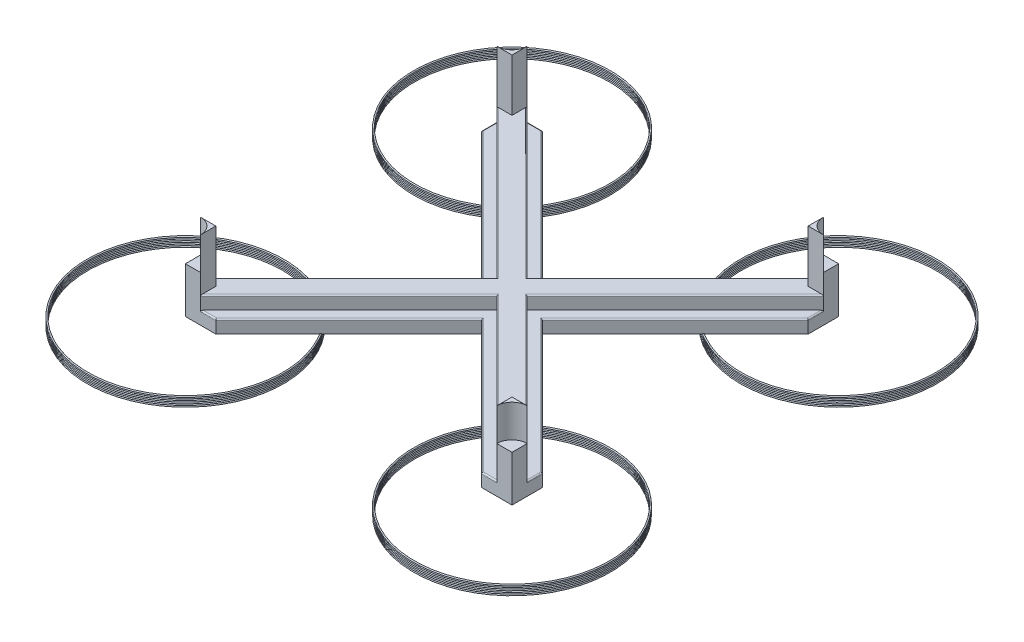
SolidWorks part; units mm, degrees
material "ABS"
ref_plane "Front Plane" through (0, 0, 0) normal (0, 0, 1) x (1, 0, 0)
ref_plane "Top Plane" through (0, 0, 0) normal (0, 1, 0) x (1, 0, 0)
ref_plane "Right Plane" through (0, 0, 0) normal (1, 0, 0) x (0, 0, -1)
sketch "Sketch1" plane through (0, 0, 0) normal (0, 1, 0) x (1, 0, 0)
  line L0 (-11.8367, 0) -> (-63.5, 51.6633)
  line L1 (-63.5, -63.5) -> (-51.6633, -63.5)
  line L2 (-63.5, -63.5) -> (-63.5, -51.6633)
  line L3 (-63.5, 63.5) -> (-51.6633, 63.5)
  line L4 (63.5, -63.5) -> (63.5, -51.6633)
  line L5 (-63.5, -63.5) -> (63.5, 63.5) construction
  line L6 (-63.5, 63.5) -> (63.5, -63.5) construction
  line L7 (0, -11.8367) -> (51.6633, -63.5)
  line L8 (0, 11.8367) -> (-51.6633, 63.5)
  line L9 (11.8367, 0) -> (63.5, -51.6633)
  line L12 (-63.5, -51.6633) -> (-11.8367, 0)
  line L13 (63.5, 51.6633) -> (11.8367, 0)
  line L16 (51.6633, 63.5) -> (63.5, 63.5)
  line L17 (63.5, 51.6633) -> (63.5, 63.5)
  line L18 (-63.5, 51.6633) -> (-63.5, 63.5)
  line L19 (51.6633, -63.5) -> (63.5, -63.5)
  line L20 (0, 11.8367) -> (51.6633, 63.5)
  line L21 (0, -11.8367) -> (-51.6633, -63.5)
  point P0 (0, 0)
extrude "Boss-Extrude1" add sketch "Sketch1" along normal blind 5.08
ref_plane "Plane3" through (0, 0, 0) normal (0, 0, -1) x (-1, 0, 0)
ref_plane "Plane1" through (0, 0, 0) normal (0.7071, 0, -0.7071) x (-0.7071, 0, -0.7071)
ref_plane "Plane2" through (0, 0, 0) normal (1, 0, 0) x (0, 0, -1)
sketch "Sketch3" plane through (0, 5.08, 0) normal (0, 1, 0) x (1, 0, 0)
  line L0 (-63.5, -63.5) -> (63.5, 63.5) construction
  line L1 (-63.5, -63.5) -> (-57.5816, -63.5)
  line L2 (-63.5, -63.5) -> (-63.5, -57.5816)
  line L3 (-63.5, -57.5816) -> (-57.5816, -57.5816)
  line L4 (-57.5816, -63.5) -> (-57.5816, -57.5816)
  line L5 (-63.5, -63.5) -> (-63.5, -51.6633) construction
  line L8 (1.9757, -1.9757) -> (-1.9757, 1.9757) construction
  line L9 (57.5816, 63.5) -> (57.5816, 57.5816)
  line L10 (63.5, 57.5816) -> (57.5816, 57.5816)
  line L11 (63.5, 63.5) -> (63.5, 57.5816)
  line L12 (63.5, 63.5) -> (57.5816, 63.5)
  line L13 (2.794, 0) -> (-2.794, 0) construction
  line L14 (-63.5, 57.5816) -> (-57.5816, 57.5816)
  line L15 (-57.5816, 63.5) -> (-57.5816, 57.5816)
  line L16 (-63.5, 63.5) -> (-57.5816, 63.5)
  line L17 (-63.5, 63.5) -> (-63.5, 57.5816)
  line L18 (0, -2.794) -> (0, 2.794) construction
  line L19 (63.5, -57.5816) -> (57.5816, -57.5816)
  line L20 (57.5816, -63.5) -> (57.5816, -57.5816)
  line L21 (63.5, -63.5) -> (57.5816, -63.5)
  line L22 (63.5, -63.5) -> (63.5, -57.5816)
extrude "Boss-Extrude2" add sketch "Sketch3" along normal blind 38.1
sketch "Sketch4" plane through (0, 0, 0) normal (0, -1, 0) x (1, 0, 0)
  circle A4 centre (-63.5, 63.5) radius 38.1
  point P12 (0, 0)
  point P14 (0, 0)
  point P21 (0, 0)
ref_plane "Plane4" through (0, 0, 0) normal (0.7071, 0, 0.7071) x (0.7071, 0, -0.7071)
sweep "Sweep11" add path "Sketch4" circular profile diameter 0.508 parameters "D3"=0.508
ref_axis "Axis1" through (0, 0, 0) along (0, 1, 0)
pattern_circular "CirPattern1" count 4 over 360 about axis through (0, 0, 0) along (0, 1, 0) of "Sweep11"
sketch "Sketch5" plane through (0, 43.18, 0) normal (0, 1, 0) x (1, 0, 0)
  circle A0 centre (63.5, -63.5) radius 5.9184
extrude "Cut-Extrude1" cut sketch "Sketch5" against normal blind 25.4
pattern_circular "CirPattern2" count 4 over 360 about axis through (0, 0, 0) along (0, 1, 0) of "Cut-Extrude1" reverse direction yes
ref_plane "Plane5" through (0, -0.508, 0) normal (0, -1, 0) x (-1, 0, 0)
ref_axis "Axis2" through (-63.5, 17.78, 63.5) along (0, -1, 0)
sketch "Sketch14" plane through (0, -0.508, 0) normal (0, -1, 0) x (-1, 0, 0)
  circle A0 centre (63.5, -63.5) radius 38.1
sweep "Sweep13" add path "Sketch14" circular profile diameter 0.508 parameters "D3"=0.508
pattern_circular "CirPattern8" count 4 over 360 about axis through (0, 0, 0) along (0, 1, 0) of bodies 109
pattern_linear "LPattern16" count 6 spacing 0.5588 along (0, -1, 0) of bodies 121 120 122 109
sketch "Sketch84" plane through (0, 5.08, 0) normal (0, 1, 0) x (1, 0, 0)
  line L0 (-63.5, 57.5816) -> (-5.9184, 0)
  line L1 (57.5816, 63.5) -> (0, 5.9184)
  line L2 (-57.5816, 63.5) -> (0, 5.9184)
  line L3 (63.5, 57.5816) -> (5.9184, 0)
  line L4 (5.9184, 0) -> (63.5, -57.5816)
  line L5 (-5.9184, 0) -> (-63.5, -57.5816)
  line L6 (0, -5.9184) -> (57.5816, -63.5)
  line L7 (0, -5.9184) -> (-57.5816, -63.5)
  line M1 (57.5816, -57.5816) -> (63.5, -57.5816)
  line M6 (63.5, 57.5816) -> (57.5816, 57.5816)
  line M7 (57.5816, 57.5816) -> (57.5816, 63.5)
  line M12 (-57.5816, 63.5) -> (-57.5816, 57.5816)
  line M13 (-57.5816, 57.5816) -> (-63.5, 57.5816)
  line M18 (-63.5, -57.5816) -> (-57.5816, -57.5816)
  line M19 (-57.5816, -57.5816) -> (-57.5816, -63.5)
  line M24 (57.5816, -63.5) -> (57.5816, -57.5816)
extrude "Boss-Extrude3" add sketch "Sketch84" along normal blind 5.08 contours L7 L6 L4 L3 L1 L2 L0 L5 M24 M1 M6 M7 M12 M13 M18 M19 region at (0, 5.08, 0)
fillet "Fillet1" radius 0.508 24 edges at (-54.6224, 5.08, -63.5) (-63.5, 5.08, -54.6224) (54.6224, 5.08, -63.5) (63.5, 5.08, -54.6224) (54.6224, 5.08, 63.5) (63.5, 5.08, 54.6224) (-63.5, 5.08, 54.6224) (-54.6224, 5.08, 63.5) (25.8316, 5.08, -37.6684) (-25.8316, 5.08, -37.6684) (-37.6684, 5.08, 25.8316) (-37.6684, 5.08, -25.8316) (37.6684, 5.08, 25.8316) (37.6684, 5.08, -25.8316) (25.8316, 5.08, 37.6684) (-25.8316, 5.08, 37.6684) (34.7092, 10.16, 28.7908) (34.7092, 10.16, -28.7908) (28.7908, 10.16, -34.7092) (-28.7908, 10.16, -34.7092) (-34.7092, 10.16, -28.7908) (-34.7092, 10.16, 28.7908) (28.7908, 10.16, 34.7092) (-28.7908, 10.16, 34.7092)
sketch "Sketch85" plane through (0, 43.18, 0) normal (0, 1, 0) x (1, 0, 0)
  line L1 (-63.5, -63.5) -> (70.1925, -63.5)
  line L2 (-63.5, -63.5) -> (-63.5, 70.1925)
  line L3 (-63.5, 70.1925) -> (70.1925, 70.1925)
  line L4 (70.1925, -63.5) -> (70.1925, 70.1925)
extrude "Cut-Extrude2" cut sketch "Sketch85" against normal blind 12.7
sketch "Sketch86" [suppressed] plane through (0, 17.78, 0) normal (0, 1, 0) x (1, 0, 0)
  line L0 (-63.5, -63.5) -> (-59.3151, -59.3151)
  line L1 (-63.5, 63.5) -> (-59.3151, 59.3151)
  line L2 (63.5, 63.5) -> (59.3151, 59.3151)
  line L3 (63.5, -63.5) -> (59.3151, -59.3151)
  circle A0 centre (-61.4075, -61.4075) radius 0.635
  circle A1 centre (-61.4075, 61.4075) radius 0.635
  circle A2 centre (61.4075, 61.4075) radius 0.635
  circle A3 centre (61.4075, -61.4075) radius 0.635
  point P2 (-61.4075, -61.4075)
  point P8 (-61.4075, 61.4075)
  point P11 (61.4075, 61.4075)
  point P14 (61.4075, -61.4075)
  point P15 (0, 0)
  point P24 (0, 0)
  dimension "D2" = 4
  dimension "D1" = 4
